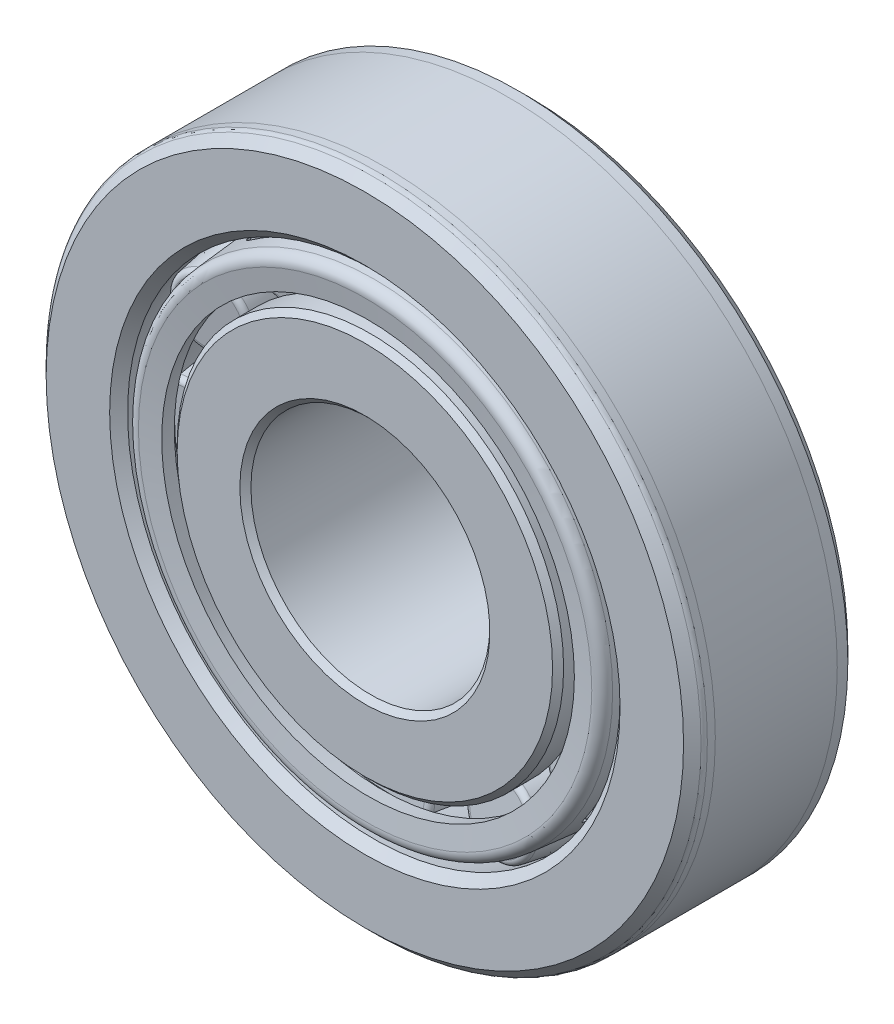
SolidWorks part; units mm, degrees
material "AISI 1020 Steel, Cold Rolled"
ref_plane "Front Plane" through (0, 0, 0) normal (0, 0, 1) x (1, 0, 0)
ref_plane "Top Plane" through (0, 0, 0) normal (0, 1, 0) x (1, 0, 0)
ref_plane "Right Plane" through (0, 0, 0) normal (1, 0, 0) x (0, 0, -1)
sketch "Sketch1" plane through (0, 0, 0) normal (1, 0, 0) x (0, 0, -1)
  line L0 (-4.3655, 17.5) -> (-4.3655, 13)
  line L1 (-4.3655, 13) -> (4.3655, 14.58)
  line L2 (4.3655, 14.58) -> (4.3655, 17.5)
  line L3 (4.3655, 17.5) -> (-4.3655, 17.5)
  line L4 (0, 0) -> (10110.1541, 0) construction
  line L5 (-1.2626, 13.5615) -> (1.1915, 0) construction
  line L6 (6.7475, 10.81) -> (6.7475, 6.35)
  line L7 (6.7475, 6.35) -> (-4.365, 6.35)
  line L8 (-4.365, 6.35) -> (-4.365, 10.2695)
  line L9 (-4.365, 10.2695) -> (-2.7491, 10.2695)
  line L10 (6.7475, 10.81) -> (3.6851, 10.81)
  line L12 (6.7475, 17.5) -> (-4.3655, 17.5) construction
  line L14 (-4.3655, 12.1389) -> (6.3809, 13.6861)
  line L15 (6.3809, 13.6861) -> (6.4935, 12.9042)
  line L16 (6.4935, 12.9042) -> (-3.471, 11.4695)
  line L17 (-3.471, 11.4695) -> (-3.4147, 11.0785)
  line L18 (-3.1733, 13.2157) -> (3.1733, 14.3643) construction
  line L19 (-4.3655, 12.1389) -> (-4.1966, 10.9659)
  line L20 (-4.1966, 10.9659) -> (-3.4147, 11.0785)
  line L21 (3.1733, 14.3643) -> (3.7913, 10.0719)
  line L22 (3.7913, 10.0719) -> (-2.6215, 9.3833)
  line L23 (-2.6215, 9.3833) -> (-3.1733, 13.2157)
  line L25 (-2.8974, 11.2995) -> (3.4823, 12.2181) construction
  line L27 (0, 13.79) -> (0.2925, 11.7588) construction
  line L28 (0.2925, 11.7588) -> (0.5849, 9.7276) construction
  line L29 (-4.3655, 17.5) -> (-4.3655, 12.1389) construction
  point P7 (0, 17.5)
  point P19 (-39.3655, 0)
  point P44 (3.4467, 12.4655)
  dimension "Width" = 8.731
  dimension "Inner Ring Width" = 11.1125
  dimension "Effective Center" = 5.556
  dimension "Width A" = 11.113
  dimension "Cone Thick" = 0.79
  dimension "D17" = 0.395
  dimension "Roller S Diameter" = 3.872
  dimension "Roller L Diameter" = 4.3366
  dimension "Roller Length" = 6.4455
  dimension "D2" = 0.25
  dimension "Back Cone Dim" = 0.254
  dimension "Diameter B" = 26
  dimension "Diameter C" = 20.539
  dimension "Diameter F" = 29.16
  dimension "Diameter E" = 21.62
  dimension "D3" = 11.113
  dimension "ID" = 12.7
  dimension "OD" = 35
  dimension "Cage Width" = 11.113
  dimension "D4" = 35
  dimension "For Housing ID" = 35
  dimension "For Shaft Diameter" = 12.7
sketch "Sketch0" plane through (0, 0, 0) normal (0, 0, 1) x (1, 0, 0)
  circle A0 centre (0, 0) radius 6.35
  circle A1 centre (0, 0) radius 17.5
  dimension "D1" = 35
  dimension "D2" = 12.7
sketch "Sketch2" plane through (0, 0, 0) normal (1, 0, 0) x (0, 0, -1)
  line L0 (-4.3655, 17.5) -> (-4.3655, 13)
  line L1 (-4.3655, 13) -> (4.3655, 14.58)
  line L2 (4.3655, 14.58) -> (4.3655, 17.5)
  line L3 (4.3655, 17.5) -> (-4.3655, 17.5)
revolve "Revolve1" add sketch "Sketch2" angle 360 about L4
sketch "Sketch3" plane through (0, 0, 0) normal (1, 0, 0) x (0, 0, -1)
  line L0 (-4.365, 10.2695) -> (-4.365, 6.35)
  line L1 (-4.365, 6.35) -> (6.7475, 6.35)
  line L2 (6.7475, 6.35) -> (6.7475, 10.81)
  line L3 (6.7475, 10.81) -> (3.6851, 10.81)
  line L4 (3.6851, 10.81) -> (3.7913, 10.0719)
  line L5 (3.7913, 10.0719) -> (-2.6215, 9.3833)
  line L6 (-2.6215, 9.3833) -> (-2.7491, 10.2695)
  line L7 (-2.7491, 10.2695) -> (-4.365, 10.2695)
revolve "Revolve2" add sketch "Sketch3" angle 360 about L4
sketch "Sketch4" plane through (0, 0, 0) normal (1, 0, 0) x (0, 0, -1)
  line L0 (6.4935, 12.9042) -> (6.3809, 13.6861)
  line L1 (6.3809, 13.6861) -> (-4.4335, 12.6113)
  line L2 (-4.4335, 12.6113) -> (-4.1966, 10.9659)
  line L3 (-4.1966, 10.9659) -> (-3.4147, 11.0785)
  line L4 (-3.4147, 11.0785) -> (-3.471, 11.4695)
  line L5 (-3.471, 11.4695) -> (6.4935, 12.9042)
  line L6 (-3.1733, 13.2157) -> (-4.3655, 12.1389) construction
  line L7 (-3.7694, 12.6773) -> (-3.1733, 13.2157) construction
  point P14 (-3.4714, 12.9465)
revolve "Revolve3" add sketch "Sketch4" angle 360 about L4
sketch "Sketch6" plane through (0, 0, 0) normal (1, 0, 0) x (0, 0, -1)
  line L0 (3.7913, 10.0719) -> (3.4823, 12.2181)
  line L1 (3.4823, 12.2181) -> (-2.8974, 11.2995)
  line L3 (-2.8974, 11.2995) -> (-2.6215, 9.3833)
  line L4 (-2.6215, 9.3833) -> (3.7913, 10.0719)
  line L5 (-2.8974, 11.2995) -> (3.4823, 12.2181) construction
  line L6 (-2.6215, 9.3833) -> (-3.1733, 13.2157) construction
revolve "Revolve4" add sketch "Sketch6" angle 360 about L25
sketch "Sketch8" plane through (0, 0.7394, -5.1351) normal (0, 0.1425, -0.9898) x (-1, 0, 0)
  line L0 (0, 9.4288) -> (0, 11.5971) construction
  circle A0 centre (0, 11.5971) radius 1.0842
  point P3 (0, 10.5129)
extrude "Cut-Extrude1" cut sketch "Sketch8" against normal blind 0.635
fillet "Fillet7" radius 0.9525 1 edges at (0, 13.2007, -2.6993)
chamfer "Chamfer4" distance 0.271 angle 45 1 edges at (0, 10.0719, -3.7913)
fillet "Fillet8" radius 0.2904 1 edges at (0, 9.3833, 2.6215)
pattern_circular "CirPattern1" count 12 over 360 about axis through (0, 0, 0) along (0, 0, 1) of "Revolve4"
fillet "Fillet9" radius 0.5461 1 edges at (12.6113, 0, 4.4335)
fillet "Fillet10" radius 0.2567 2 edges at (13.6861, 0, -6.3809) (12.9042, 0, -6.4935)
sketch "Sketch9" plane through (0, 0, 0) normal (1, 0, 0) x (0, 0, -1)
  line L0 (-2.8974, 11.2995) -> (3.4823, 12.2181)
  line L1 (3.4823, 12.2181) -> (3.8121, 9.9281)
  line L2 (3.8121, 9.9281) -> (-2.6008, 9.2395)
  line L3 (-2.6008, 9.2395) -> (-2.8974, 11.2995)
  line L4 (-2.6215, 9.3833) -> (3.7913, 10.0719) construction
  dimension "D1" = 0.1452
revolve "Cut-Revolve2" cut sketch "Sketch9" angle 360 about L0
fillet "Fillet11" radius 0.1936 4 edges at (-1.9392, 12.0477, 3.0051) (1.9392, 12.0477, 3.0051) (2.2503, 12.75, -3.4057) (-2.2503, 12.75, -3.4057)
pattern_circular "CirPattern2" count 12 over 360 about axis through (0, 0, 0) along (0, 0, 1) of "Cut-Revolve2", "Fillet11"
chamfer "Chamfer1" distance 0.5625 angle 45 1 edges at (17.5, 0, 4.3655)
ref_plane "Plane1" through (0, 0, 3.2405) normal (0, 0, 1) x (1, 0, 0)
ref_plane "Plane2" through (0, 0, -3.2405) normal (0, 0, -1) x (-1, 0, 0)
split line "Split Line1"
split line "Split Line2"
fillet "Fillet6" radius 0.3375 1 edges at (-17.5, 0, 3.803)
chamfer "Chamfer2" distance 0.294 angle 45 2 edges at (10.2695, 0, 4.365) (6.35, 0, 4.365)
chamfer "Chamfer3" distance 0.446 angle 45 2 edges at (6.35, 0, -6.7475) (10.81, 0, -6.7475)
chamfer "Chamfer5" distance 0.5625 angle 45 1 edges at (17.5, 0, -4.3655)
chamfer "Chamfer6" distance 0.1688 angle 45 1 edges at (14.58, 0, -4.3655)
sketch "Sketch7" plane through (0, 0, 0) normal (1, 0, 0) x (0, 0, -1)
  line L0 (6.7475, 10.81) -> (6.7475, 6.35) construction
  line L1 (-4.365, 10.2695) -> (-2.7491, 10.2695) construction
  line L2 (-4.365, 6.35) -> (-4.365, 10.2695) construction
  line L3 (6.7475, 6.35) -> (-4.365, 6.35) construction
  line L4 (6.7475, 10.81) -> (3.6851, 10.81) construction
  line L5 (3.7913, 10.0719) -> (-2.6215, 9.3833) construction
  line L6 (3.1733, 14.3643) -> (3.7913, 10.0719) construction
  line L7 (-4.3655, 13) -> (4.3655, 14.58) construction
  line L8 (-2.6215, 9.3833) -> (-3.1733, 13.2157) construction
  line L9 (6.7475, 10.81) -> (6.7475, 6.35)
  line L10 (-4.365, 10.2695) -> (-2.7491, 10.2695)
  line L11 (-4.365, 6.35) -> (-4.365, 10.2695)
  line L12 (6.7475, 6.35) -> (-4.365, 6.35)
  line L13 (6.7475, 10.81) -> (3.6851, 10.81)
  line L14 (3.7913, 10.0719) -> (-2.6215, 9.3833)
  line L15 (3.1733, 14.3643) -> (3.7913, 10.0719)
  line L16 (-3.1733, 13.2157) -> (3.1733, 14.3643)
  line L17 (-2.6215, 9.3833) -> (-3.1733, 13.2157)
  line L18 (0, 0) -> (6.7475, 0) construction
  line L21 (-2.6215, -9.3833) -> (-3.1733, -13.2157)
  line L22 (-3.1733, -13.2157) -> (3.1733, -14.3643)
  line L23 (3.1733, -14.3643) -> (3.7913, -10.0719)
  line L24 (3.7913, -10.0719) -> (-2.6215, -9.3833)
  line L25 (6.7475, -10.81) -> (3.6851, -10.81)
  line L26 (6.7475, -6.35) -> (-4.365, -6.35)
  line L27 (-4.365, -6.35) -> (-4.365, -10.2695)
  line L28 (-4.365, -10.2695) -> (-2.7491, -10.2695)
  line L29 (6.7475, -10.81) -> (6.7475, -6.35)
equation "\"D17@Sketch1\" = \"Cone Thick@Sketch1\" / 2"
equation "\"D1@Chamfer1\"=(\"OD@Sketch1\"-\"Diameter B@Sketch1\")*0.5*0.125"
equation "\"D1@Plane1\"=(\"OD@Sketch1\"-\"Diameter B@Sketch1\")*0.5*0.25"
equation "\"D1@Plane2\"=(\"OD@Sketch1\"-\"Diameter B@Sketch1\")*0.5*0.25"
equation "\"D1@Fillet6\"=(\"OD@Sketch1\"-\"Diameter B@Sketch1\")*0.5*0.075"
equation "\"D1@Chamfer2\"=(\"Diameter C@Sketch1\"-\"ID@Sketch1\")*0.5*0.075"
equation "\"D1@Chamfer3\"=(\"Diameter E@Sketch1\"-\"ID@Sketch1\")*0.5*0.1"
equation "\"D1@Chamfer4\"=\"Roller L Diameter@Sketch1\"*0.0625"
equation "\"D1@Fillet8\"=\"Roller S Diameter@Sketch1\"*0.075"
equation "\"D1@Fillet9\"=(\"Diameter B@Sketch1\"-\"Diameter C@Sketch1\")*0.5*0.2"
equation "\"D1@Fillet10\"=\"Cone Thick@Sketch1\"*0.325"
equation "\"D1@Sketch9\"=\"Roller S Diameter@Sketch1\"*0.0375"
equation "\"D1@Fillet11\"=\"Roller S Diameter@Sketch1\"*0.05"
equation "\"D1@CirPattern2\"=\"Number of Rollers@CirPattern1\""
equation "\"D1@Chamfer5\"=\"D1@Chamfer1\""
equation "\"D1@Chamfer6\"=\"D1@Chamfer5\"*.3"
equation "\"Roller L Diameter@Sketch1\"=\"Roller S Diameter@Sketch1\"*1.12"
equation "\"Roller Length@Sketch1\"=\"Width A@Sketch1\"*.58"
equation "\"Diameter C@Sketch1\"=\"Diameter E@Sketch1\"*.95"
equation "\"D4@Sketch1\"=\"OD@Sketch1\""
